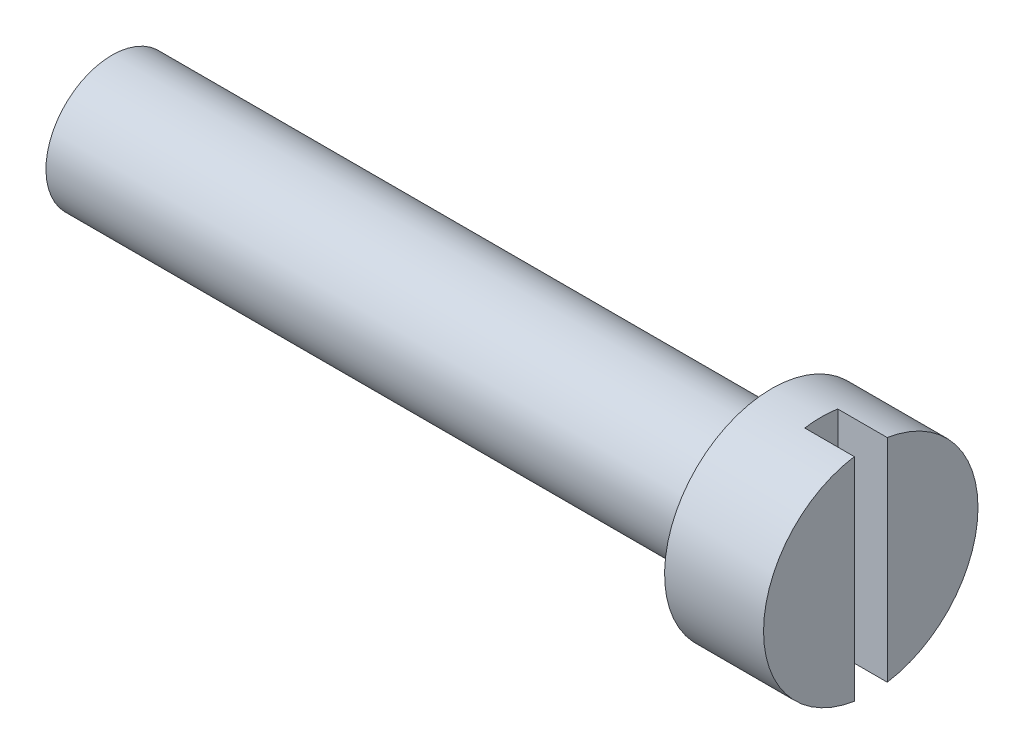
SolidWorks part; units mm, degrees
material "AISI 316 Stainless Steel Sheet (SS)"
ref_plane "Front Plane" through (0, 0, 0) normal (0, 0, 1) x (1, 0, 0)
ref_plane "Top Plane" through (0, 0, 0) normal (0, 1, 0) x (1, 0, 0)
ref_plane "Right Plane" through (0, 0, 0) normal (1, 0, 0) x (0, 0, -1)
sketch "Sketch1" plane through (0, 0, 0) normal (0, 0, 1) x (1, 0, 0)
  line L0 (0, 0) -> (-23, 0)
  line L1 (-23, 0) -> (-23, 2)
  line L2 (-23, 2) -> (-3, 2)
  line L3 (-3, 2) -> (-3, 3.25)
  line L4 (-3, 3.25) -> (0, 3.25)
  line L5 (0, 3.25) -> (0, 0)
  dimension "D1" = 3
  dimension "D2" = 20
  dimension "D3" = 2
  dimension "D4" = 3.25
revolve "Revolve1" add sketch "Sketch1" angle 360 about L0
sketch "Sketch2" plane through (0, 0, 0) normal (1, 0, 0) x (0, 0, -1)
  line L1 (-0.5, -3.25) -> (0.5, -3.25)
  line L2 (-0.5, -3.25) -> (-0.5, 3.25)
  line L3 (-0.5, 3.25) -> (0.5, 3.25)
  line L4 (0.5, -3.25) -> (0.5, 3.25)
  line L5 (-0.5, -3.25) -> (0.5, 3.25) construction
  line L6 (-0.5, 3.25) -> (0.5, -3.25) construction
  circle A0 centre (0, 0) radius 3.25 construction
  point P0 (0, 0)
  dimension "D1" = 1
extrude "Cut-Extrude1" cut sketch "Sketch2" against normal blind 1.5
move or copy body "Body-Move/Copy4" [suppressed] bodies to move or copy 102 parameters "D1"=0, "D2"=0, "D3"=0
move or copy body "Body-Move/Copy3" [suppressed] bodies to move or copy 102 parameters "D1"=0, "D2"=0, "D3"=0
move or copy body "Body-Move/Copy2" [suppressed] bodies to move or copy 102 parameters "D1"=0, "D2"=0, "D3"=0
move or copy body "Body-Move/Copy1" [suppressed] bodies to move or copy 102 parameters "D1"=0, "D2"=0, "D3"=0
